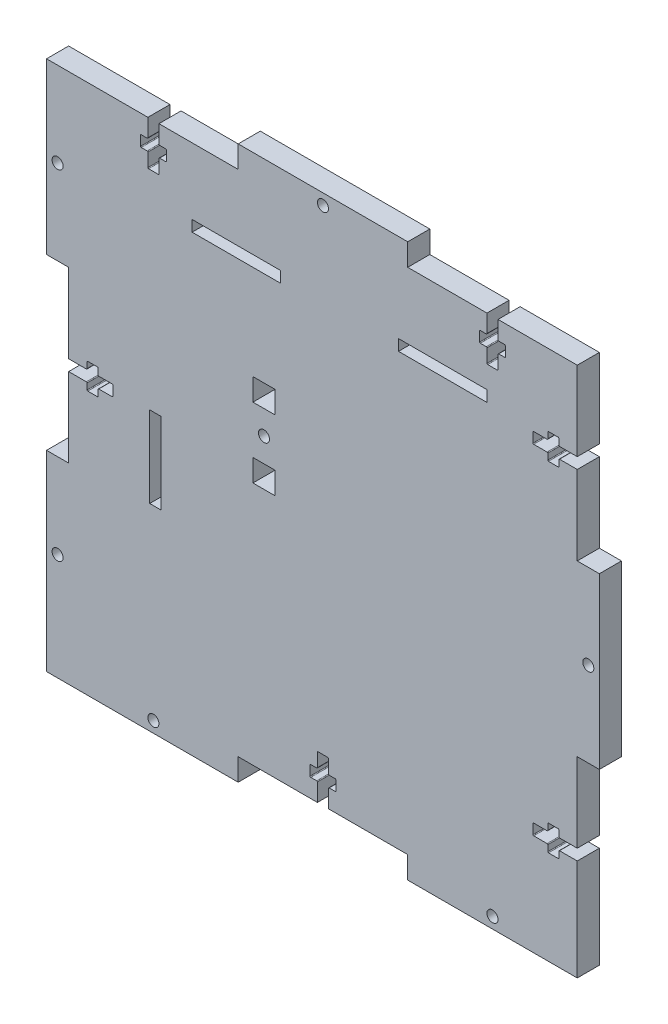
SolidWorks part; units mm, degrees
ref_plane "Front Plane" through (0, 0, 0) normal (0, 0, 1) x (1, 0, 0)
ref_plane "Top Plane" through (0, 0, 0) normal (0, 1, 0) x (1, 0, 0)
ref_plane "Right Plane" through (0, 0, 0) normal (1, 0, 0) x (0, 0, -1)
sketch "Sketch1" plane through (0, 0, 0) normal (0, 0, 1) x (1, 0, 0)
  line L0 (-69, 69) -> (-23, 69)
  line L5 (-75, -75) -> (75, -75) construction
  line L6 (-75, -75) -> (-75, 75) construction
  line L7 (-75, 75) -> (75, 75) construction
  line L8 (75, -75) -> (75, 75) construction
  line L9 (75, 23) -> (69, 23)
  line L10 (69, -23) -> (75, -23)
  line L11 (-69, -69) -> (69, -69) construction
  line L12 (-69, -69) -> (-69, 69) construction
  line L13 (-69, 69) -> (69, 69) construction
  line L14 (69, -69) -> (69, 69) construction
  line L15 (-69, -69) -> (69, 69) construction
  line L16 (69, -69) -> (69, -23)
  line L17 (-23, 69) -> (-23, 75)
  line L18 (-23, 75) -> (23, 75)
  line L19 (23, 75) -> (23, 69)
  line L20 (23, 69) -> (69, 69)
  line L21 (75, -23) -> (75, 23)
  line L22 (69, 23) -> (69, 69)
  line L23 (-75, 23) -> (-69, 23)
  line L24 (-69, 69) -> (-75, 69)
  line L25 (-75, 69) -> (-75, 23)
  line L26 (69, -69) -> (69, -75)
  line L27 (69, -75) -> (23, -75)
  line L28 (23, -75) -> (23, -69)
  line L29 (23, -69) -> (-23, -69)
  line L30 (-23, -69) -> (-23, -75)
  line L31 (-23, -75) -> (-69, -75)
  line L32 (-69, -75) -> (-69, -69) construction
  line L33 (-69, 23) -> (-69, -23)
  line L34 (-69, -23) -> (-75, -23)
  line L35 (-75, -23) -> (-75, -69)
  line L36 (-75, -69) -> (-69, -69) construction
  line L37 (-46, 69) -> (-46, -75) construction
  line L38 (-69, 69) -> (69, -69) construction
  line L39 (-75, -75) -> (-69, -75)
  line L40 (-75, -75) -> (-75, -69)
  point P0 (0, 0)
  point P6 (-7, -7)
  point P26 (0, -75)
  point P27 (-75, 0)
  dimension "D1" = 150
  dimension "D2" = 150
  dimension "D5" = 46
  dimension "D3" = 6
  dimension "D6" = 6
  dimension "D7" = 6
extrude "Box Side" add sketch "Sketch1" along normal blind 6
sketch "Sketch2" plane through (0, 0, 6) normal (0, 0, 1) x (1, 0, 0)
  line L0 (23, 72) -> (-23, 72) construction
  line L1 (23, 75) -> (23, 69) construction
  line L2 (-23, 69) -> (-23, 75) construction
  line L3 (-46, 69) -> (-46, -75) construction
  line L5 (0, 75) -> (0, 69) construction
  line L6 (-23, 75) -> (23, 75) construction
  line L7 (-69, 69) -> (69, 69) construction
  line L16 (-46, 69) -> (-46, -75) construction
  line L21 (0, -69) -> (0, 69) construction
  line L35 (-69, 69) -> (-23, 69) construction
  line L36 (-44.5, 69) -> (-44.5, 64.2)
  line L37 (-44.3, 64) -> (-42.7, 64)
  line L38 (-42.5, 63.8) -> (-42.5, 61.2)
  line L39 (-42.7, 61) -> (-44.3, 61)
  line L40 (-44.5, 60.8) -> (-44.5, 57.2)
  line L46 (-44.7, 57) -> (-47.3, 57)
  line L48 (-44.5, 69) -> (-47.5, 69)
  line L51 (-47.5, 60.8) -> (-47.5, 57.2)
  line L52 (-49.3, 61) -> (-47.7, 61)
  line L53 (-49.5, 63.8) -> (-49.5, 61.2)
  line L54 (-47.7, 64) -> (-49.3, 64)
  line L55 (-47.5, 69) -> (-47.5, 64.2)
  line L56 (47.5, 69) -> (47.5, 64.2)
  line L57 (47.7, 64) -> (49.3, 64)
  line L58 (49.5, 63.8) -> (49.5, 61.2)
  line L59 (49.3, 61) -> (47.7, 61)
  line L60 (47.5, 60.8) -> (47.5, 57.2)
  line L61 (44.5, 69) -> (47.5, 69)
  line L62 (44.7, 57) -> (47.3, 57)
  line L63 (44.5, 60.8) -> (44.5, 57.2)
  line L64 (42.7, 61) -> (44.3, 61)
  line L65 (42.5, 63.8) -> (42.5, 61.2)
  line L66 (44.3, 64) -> (42.7, 64)
  line L67 (44.5, 69) -> (44.5, 64.2)
  line L68 (-69, -69) -> (69, 69) construction
  line L69 (-69, -69) -> (69, 69) construction
  line L70 (75, 0) -> (69, 0) construction
  line L71 (72, 23) -> (72, -23) construction
  line L72 (69, 44.5) -> (64.2, 44.5)
  line L73 (64, 44.3) -> (64, 42.7)
  line L74 (63.8, 42.5) -> (61.2, 42.5)
  line L75 (61, 42.7) -> (61, 44.3)
  line L76 (60.8, 44.5) -> (57.2, 44.5)
  line L77 (57, 44.7) -> (57, 47.3)
  line L78 (69, 44.5) -> (69, 47.5)
  line L79 (60.8, 47.5) -> (57.2, 47.5)
  line L80 (61, 49.3) -> (61, 47.7)
  line L81 (63.8, 49.5) -> (61.2, 49.5)
  line L82 (64, 47.7) -> (64, 49.3)
  line L83 (69, 47.5) -> (64.2, 47.5)
  line L84 (69, -47.5) -> (64.2, -47.5)
  line L85 (64, -47.7) -> (64, -49.3)
  line L86 (63.8, -49.5) -> (61.2, -49.5)
  line L87 (61, -49.3) -> (61, -47.7)
  line L88 (60.8, -47.5) -> (57.2, -47.5)
  line L89 (69, -44.5) -> (69, -47.5)
  line L90 (57, -44.7) -> (57, -47.3)
  line L91 (60.8, -44.5) -> (57.2, -44.5)
  line L92 (61, -42.7) -> (61, -44.3)
  line L93 (63.8, -42.5) -> (61.2, -42.5)
  line L94 (64, -44.3) -> (64, -42.7)
  line L95 (69, -44.5) -> (64.2, -44.5)
  line L120 (-69, 69) -> (69, -69) construction
  line L121 (-69, 69) -> (69, -69) construction
  line L122 (-1.5, -69) -> (1.5, -69)
  line L123 (-23, -69) -> (23, -69) construction
  line L124 (1.5, -69) -> (1.5, -64.2)
  line L125 (1.7, -64) -> (3.3, -64)
  line L126 (3.5, -63.8) -> (3.5, -61.2)
  line L127 (3.3, -61) -> (1.7, -61)
  line L128 (1.5, -60.8) -> (1.5, -57.2)
  line L129 (1.3, -57) -> (-1.3, -57)
  line L130 (-1.5, -60.8) -> (-1.5, -57.2)
  line L131 (-3.3, -61) -> (-1.7, -61)
  line L132 (-3.5, -63.8) -> (-3.5, -61.2)
  line L133 (-1.7, -64) -> (-3.3, -64)
  line L134 (-1.5, -69) -> (-1.5, -64.2)
  line L135 (-69, -1.5) -> (-64.2, -1.5)
  line L136 (-64, -1.7) -> (-64, -3.3)
  line L137 (-63.8, -3.5) -> (-61.2, -3.5)
  line L138 (-61, -3.3) -> (-61, -1.7)
  line L139 (-60.8, -1.5) -> (-57.2, -1.5)
  line L140 (-57, 1.3) -> (-57, -1.3)
  line L141 (-60.8, 1.5) -> (-57.2, 1.5)
  line L142 (-61, 3.3) -> (-61, 1.7)
  line L143 (-63.8, 3.5) -> (-61.2, 3.5)
  line L144 (-64, 1.7) -> (-64, 3.3)
  line L145 (-69, 1.5) -> (-64.2, 1.5)
  line L146 (-69, -1.5) -> (-69, 1.5)
  line L147 (-69, -72) -> (-23, -72) construction
  line L148 (-23, 69) -> (-75, 69) construction
  line L149 (-23, -75) -> (-23, -69) construction
  line L150 (-69, -69) -> (-69, -75) construction
  line L151 (-75, -75) -> (-23, -75) construction
  circle A0 centre (0, 72) radius 1.5
  arc A1 (-44.5, 57.2) -> (-44.7, 57) centre (-44.7, 57.2) cw
  arc A2 (-44.3, 61) -> (-44.5, 60.8) centre (-44.3, 60.8) ccw
  arc A3 (-42.5, 61.2) -> (-42.7, 61) centre (-42.7, 61.2) cw
  arc A4 (-42.7, 64) -> (-42.5, 63.8) centre (-42.7, 63.8) cw
  arc A5 (-44.5, 64.2) -> (-44.3, 64) centre (-44.3, 64.2) ccw
  arc A6 (-47.5, 64.2) -> (-47.7, 64) centre (-47.7, 64.2) cw
  arc A7 (-49.3, 64) -> (-49.5, 63.8) centre (-49.3, 63.8) ccw
  arc A8 (-49.5, 61.2) -> (-49.3, 61) centre (-49.3, 61.2) ccw
  arc A9 (-47.7, 61) -> (-47.5, 60.8) centre (-47.7, 60.8) cw
  arc A10 (-47.5, 57.2) -> (-47.3, 57) centre (-47.3, 57.2) ccw
  arc A11 (47.5, 57.2) -> (47.3, 57) centre (47.3, 57.2) cw
  arc A12 (47.7, 61) -> (47.5, 60.8) centre (47.7, 60.8) ccw
  arc A13 (49.5, 61.2) -> (49.3, 61) centre (49.3, 61.2) cw
  arc A14 (49.3, 64) -> (49.5, 63.8) centre (49.3, 63.8) cw
  arc A15 (47.5, 64.2) -> (47.7, 64) centre (47.7, 64.2) ccw
  arc A16 (44.5, 64.2) -> (44.3, 64) centre (44.3, 64.2) cw
  arc A17 (42.7, 64) -> (42.5, 63.8) centre (42.7, 63.8) ccw
  arc A18 (42.5, 61.2) -> (42.7, 61) centre (42.7, 61.2) ccw
  arc A19 (44.3, 61) -> (44.5, 60.8) centre (44.3, 60.8) cw
  arc A20 (44.5, 57.2) -> (44.7, 57) centre (44.7, 57.2) ccw
  arc A21 (57.2, 44.5) -> (57, 44.7) centre (57.2, 44.7) cw
  arc A22 (61, 44.3) -> (60.8, 44.5) centre (60.8, 44.3) ccw
  arc A23 (61.2, 42.5) -> (61, 42.7) centre (61.2, 42.7) cw
  arc A24 (64, 42.7) -> (63.8, 42.5) centre (63.8, 42.7) cw
  arc A25 (64.2, 44.5) -> (64, 44.3) centre (64.2, 44.3) ccw
  arc A26 (64.2, 47.5) -> (64, 47.7) centre (64.2, 47.7) cw
  arc A27 (64, 49.3) -> (63.8, 49.5) centre (63.8, 49.3) ccw
  arc A28 (61.2, 49.5) -> (61, 49.3) centre (61.2, 49.3) ccw
  arc A29 (61, 47.7) -> (60.8, 47.5) centre (60.8, 47.7) cw
  arc A30 (57.2, 47.5) -> (57, 47.3) centre (57.2, 47.3) ccw
  arc A31 (57.2, -47.5) -> (57, -47.3) centre (57.2, -47.3) cw
  arc A32 (61, -47.7) -> (60.8, -47.5) centre (60.8, -47.7) ccw
  arc A33 (61.2, -49.5) -> (61, -49.3) centre (61.2, -49.3) cw
  arc A34 (64, -49.3) -> (63.8, -49.5) centre (63.8, -49.3) cw
  arc A35 (64.2, -47.5) -> (64, -47.7) centre (64.2, -47.7) ccw
  arc A36 (64.2, -44.5) -> (64, -44.3) centre (64.2, -44.3) cw
  arc A37 (64, -42.7) -> (63.8, -42.5) centre (63.8, -42.7) ccw
  arc A38 (61.2, -42.5) -> (61, -42.7) centre (61.2, -42.7) ccw
  arc A39 (61, -44.3) -> (60.8, -44.5) centre (60.8, -44.3) cw
  arc A40 (57.2, -44.5) -> (57, -44.7) centre (57.2, -44.7) ccw
  circle A41 centre (72, 0) radius 1.5
  arc A62 (1.5, -57.2) -> (1.3, -57) centre (1.3, -57.2) ccw
  arc A63 (1.7, -61) -> (1.5, -60.8) centre (1.7, -60.8) cw
  arc A64 (3.5, -61.2) -> (3.3, -61) centre (3.3, -61.2) ccw
  arc A65 (3.3, -64) -> (3.5, -63.8) centre (3.3, -63.8) ccw
  arc A66 (1.5, -64.2) -> (1.7, -64) centre (1.7, -64.2) cw
  arc A67 (-1.5, -64.2) -> (-1.7, -64) centre (-1.7, -64.2) ccw
  arc A68 (-3.3, -64) -> (-3.5, -63.8) centre (-3.3, -63.8) cw
  arc A69 (-3.5, -61.2) -> (-3.3, -61) centre (-3.3, -61.2) cw
  arc A70 (-1.7, -61) -> (-1.5, -60.8) centre (-1.7, -60.8) ccw
  arc A71 (-1.5, -57.2) -> (-1.3, -57) centre (-1.3, -57.2) cw
  arc A72 (-57.2, -1.5) -> (-57, -1.3) centre (-57.2, -1.3) ccw
  arc A73 (-61, -1.7) -> (-60.8, -1.5) centre (-60.8, -1.7) cw
  arc A74 (-61.2, -3.5) -> (-61, -3.3) centre (-61.2, -3.3) ccw
  arc A75 (-64, -3.3) -> (-63.8, -3.5) centre (-63.8, -3.3) ccw
  arc A76 (-64.2, -1.5) -> (-64, -1.7) centre (-64.2, -1.7) cw
  arc A77 (-64.2, 1.5) -> (-64, 1.7) centre (-64.2, 1.7) ccw
  arc A78 (-64, 3.3) -> (-63.8, 3.5) centre (-63.8, 3.3) cw
  arc A79 (-61.2, 3.5) -> (-61, 3.3) centre (-61.2, 3.3) cw
  arc A80 (-61, 1.7) -> (-60.8, 1.5) centre (-60.8, 1.7) ccw
  arc A81 (-57.2, 1.5) -> (-57, 1.3) centre (-57.2, 1.3) cw
  circle A82 centre (-46, -72) radius 1.5
  circle A83 centre (46, -72) radius 1.5
  circle A84 centre (-72, 46) radius 1.5
  circle A85 centre (-72, -46) radius 1.5
  point P6 (0, 72)
  point P38 (0, 0)
  point P56 (-46, 57)
  point P88 (46, 57)
  point P161 (57, 46)
  point P162 (57, -46)
  point P198 (0, -57)
  point P231 (-57, 0)
  point P234 (-42.5, 62.5)
  dimension "D1" = 3
  dimension "D2" = 0.2
  dimension "D8" = 0.2
  dimension "D14" = 3
  dimension "D4" = 3
  dimension "D7" = 1.5
  dimension "D10" = 3
  dimension "D12" = 1.5
  dimension "D9" = 12
  dimension "D11" = 5
  dimension "D13" = 7
  dimension "D3" = 12
  dimension "D5" = 7
  dimension "D6" = 5
extrude "Screw Cut-outs" cut sketch "Sketch2" against normal through all
sketch "Sketch3" plane through (0, 0, 6) normal (0, 0, 1) x (1, 0, 0)
  line L0 (69, 23) -> (69, 44.5) construction
  line L1 (44.5, 51) -> (20.5, 51)
  line L2 (44.5, 51) -> (44.5, 48)
  line L3 (44.5, 48) -> (20.5, 48)
  line L4 (20.5, 51) -> (20.5, 48)
  line L5 (44.5, 69) -> (23, 69) construction
  line L6 (75, -23) -> (75, 23) construction
  line L7 (-13, 22.32) -> (-19, 22.32)
  line L8 (-13, 22.32) -> (-13, 16.32)
  line L9 (-13, 16.32) -> (-19, 16.32)
  line L10 (-19, 22.32) -> (-19, 16.32)
  line L11 (-13, 3.32) -> (-19, 3.32)
  line L12 (-13, 3.32) -> (-13, -2.68)
  line L13 (-13, -2.68) -> (-19, -2.68)
  line L14 (-19, 3.32) -> (-19, -2.68)
  line L15 (-23, -69) -> (-1.5, -69) construction
  line L16 (-16, 3.32) -> (-16, 16.32) construction
  line L17 (-75, -23) -> (-75, -75) construction
  line L18 (-11.5, 51) -> (-35.5, 51)
  line L19 (-11.5, 51) -> (-11.5, 48)
  line L20 (-11.5, 48) -> (-35.5, 48)
  line L21 (-35.5, 51) -> (-35.5, 48)
  line L22 (-44, 0.5) -> (-47, 0.5)
  line L23 (-44, 0.5) -> (-44, -21.5)
  line L24 (-44, -21.5) -> (-47, -21.5)
  line L25 (-47, 0.5) -> (-47, -21.5)
  line L26 (-75, -75) -> (-23, -75) construction
  circle A0 centre (-16, 9.82) radius 1.5
  point P22 (-16, 16.32)
  point P27 (-16, 9.82)
  dimension "D9" = 3
  dimension "D1" = 3
  dimension "D2" = 24.5
  dimension "D3" = 24
  dimension "D4" = 18
  dimension "D5" = 6
  dimension "D6" = 88
  dimension "D7" = 66.32
  dimension "D8" = 13
  dimension "D10" = 32
  dimension "D11" = 22
  dimension "D12" = 3
  dimension "D13" = 28
  dimension "D14" = 53.5
extrude "Grooves" cut sketch "Sketch3" against normal through all
equation "\"filletRadius\"=0.2"
equation "\"D8@Sketch2\"=\"filletRadius\""
equation "\"D2@Sketch2\"=\"filletRadius\""
equation "\"fingerWidth\"= 46"
equation "\"D5@Sketch1\"=\"fingerWidth\""
equation "\"wallThickness\"= 6"
equation "\"D3@Sketch1\" = \"wallThickness\""
equation "\"D6@Sketch1\" = \"wallThickness\""
equation "\"D7@Sketch1\" = \"wallThickness\""
equation "\"D1@Box Side\" = \"wallThickness\""
equation "\"M3\"= 3"
equation "\"D14@Sketch2\"=\"M3\""
equation "\"D1@Sketch2\"=\"M3\""
equation "\"D12@Sketch2\"=\"M3\"/2"
equation "\"nutThickness\"=3"
equation "\"D10@Sketch2\" = \"nutThickness\""
equation "\"boltLength\"= 12"
equation "\"D9@Sketch2\" = \"boltLength\""
equation "\"distanceToNut\"= 5"
equation "\"D11@Sketch2\" = \"distanceToNut\""
equation "\"D13@Sketch2\" = \"nutWidth\""
equation "\"D7@Sketch2\"=\"M3\"/2"
equation "\"D4@Sketch2\" = \"nutThickness\""
equation "\"D3@Sketch2\" = \"boltLength\""
equation "\"D5@Sketch2\" = \"nutWidth\""
equation "\"D6@Sketch2\" = \"distanceToNut\""
equation "\"sideLength\"=150"
equation "\"D1@Sketch1\"=\"sideLength\""
equation "\"D2@Sketch1\"=\"sideLength\""
equation "\"nutWidth\"=7"
